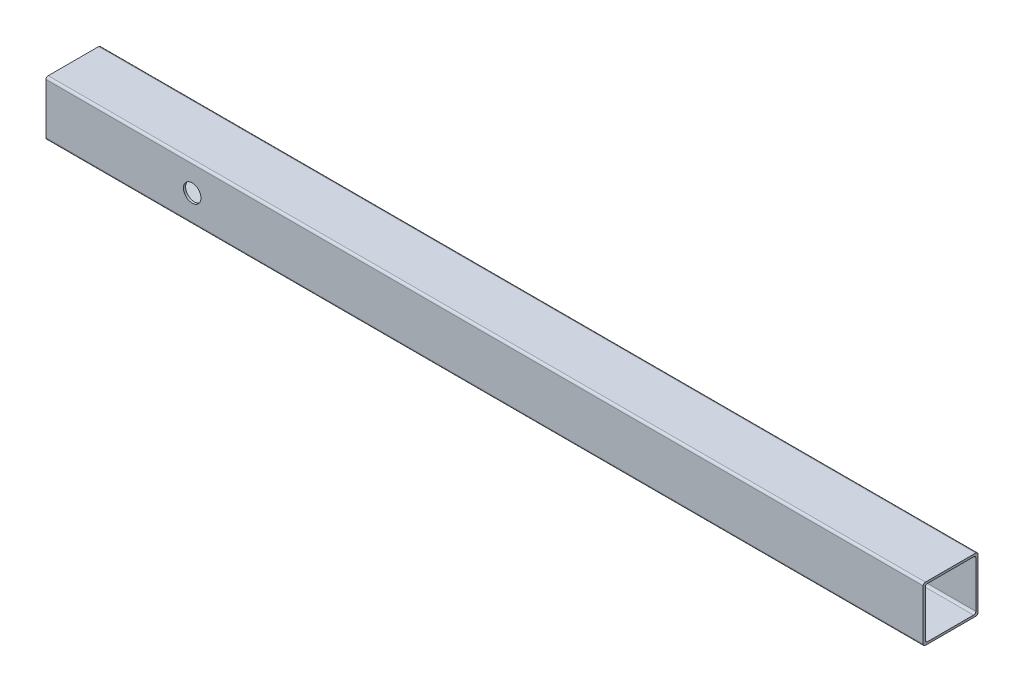
SolidWorks part; units mm, degrees
material "Thornel Mat VMA"
ref_plane "Front Plane" through (0, 0, 0) normal (0, 0, 1) x (1, 0, 0)
ref_plane "Top Plane" through (0, 0, 0) normal (0, 1, 0) x (1, 0, 0)
ref_plane "Right Plane" through (0, 0, 0) normal (1, 0, 0) x (0, 0, -1)
sketch "Sketch2" plane through (0, 0, 0) normal (1, 0, 0) x (0, 0, -1)
  line L1 (0.762, 0) -> (18.288, 0)
  line L2 (0, 0.762) -> (0, 18.288)
  line L3 (0.762, 19.05) -> (18.288, 19.05)
  line L4 (19.05, 0.762) -> (19.05, 18.288)
  line L5 (1.524, 0.762) -> (17.526, 0.762)
  line L6 (0.762, 1.524) -> (0.762, 17.526)
  line L7 (1.524, 18.288) -> (17.526, 18.288)
  line L8 (18.288, 1.524) -> (18.288, 17.526)
  arc A0 (17.526, 18.288) -> (18.288, 17.526) centre (17.526, 17.526) cw
  arc A1 (17.526, 0.762) -> (18.288, 1.524) centre (17.526, 1.524) ccw
  arc A2 (1.524, 0.762) -> (0.762, 1.524) centre (1.524, 1.524) cw
  arc A3 (0.762, 17.526) -> (1.524, 18.288) centre (1.524, 17.526) cw
  arc A4 (18.288, 19.05) -> (19.05, 18.288) centre (18.288, 18.288) cw
  arc A5 (18.288, 0) -> (19.05, 0.762) centre (18.288, 0.762) ccw
  arc A6 (0.762, 0) -> (0, 0.762) centre (0.762, 0.762) cw
  arc A7 (0, 18.288) -> (0.762, 19.05) centre (0.762, 18.288) cw
  point P11 (18.288, 18.288)
  point P14 (18.288, 0.762)
  point P19 (0.762, 18.288)
  point P22 (19.05, 19.05)
  point P25 (19.05, 0)
  point P28 (0, 0)
  point P31 (0, 19.05)
  dimension "D7" = 0.762
  dimension "D1" = 19.05
  dimension "D2" = 19.05
  dimension "D5" = 0.762
  dimension "D6" = 0.762
  dimension "D3" = 0.762
  dimension "D4" = 0.762
extrude "Boss-Extrude1" add sketch "Sketch2" along normal blind 304.8
sketch "Sketch3" plane through (0, 0, 0) normal (0, 0, 1) x (1, 0, 0)
  line L0 (0, 18.288) -> (0, 0.762) construction
  line L1 (304.8, 19.05) -> (0, 19.05) construction
  circle A0 centre (50.8, 9.525) radius 3.048
  dimension "D1" = 6.096
  dimension "D2" = 50.8
  dimension "D3" = 9.525
extrude "Cut-Extrude1" cut sketch "Sketch3" against normal up to surface (19.05 mm away) up to face at (152.4, 9.525, -19.05)
equation "\"shaft\"=0.75"
equation "\"D1@Sketch2\"=\"shaft\""
equation "\"D2@Sketch2\"=\"shaft\""
equation "\"IDshaft\"=0.4375"
equation "\"D3@Sketch3\"=\"shaft\"/2"
